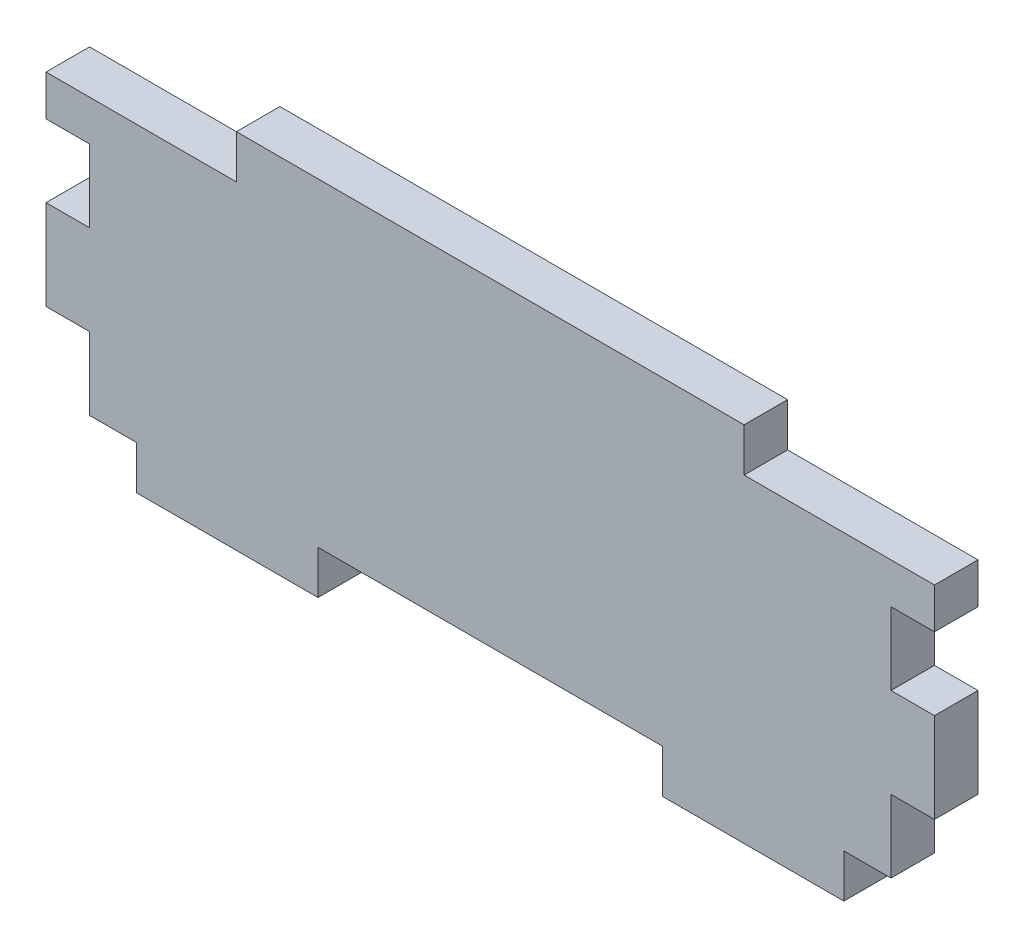
SolidWorks part; units mm, degrees
ref_plane "Front Plane" through (0, 0, 0) normal (0, 0, 1) x (1, 0, 0)
ref_plane "Top Plane" through (0, 0, 0) normal (0, 1, 0) x (1, 0, 0)
ref_plane "Right Plane" through (0, 0, 0) normal (1, 0, 0) x (0, 0, -1)
sketch "Sketch1" plane through (0, 0, 0) normal (0, 0, 1) x (1, 0, 0)
  line L0 (3.048, 9.8044) -> (0, 9.8044) construction
  line L1 (3.048, 16.1036) -> (3.048, 9.8044) construction
  line L2 (3.048, 16.1036) -> (0, 16.1036) construction
  line L3 (0, 21.1836) -> (0, 16.1036) construction
  line L4 (3.048, 21.1836) -> (0, 21.1836) construction
  line L5 (3.048, 24.0284) -> (3.048, 21.1836) construction
  line L7 (3.048, 9.8044) -> (0, 9.8044)
  line L8 (3.048, 16.1036) -> (3.048, 9.8044)
  line L9 (3.048, 16.1036) -> (0, 16.1036)
  line L10 (0, 21.1836) -> (0, 16.1036)
  line L11 (3.048, 21.1836) -> (0, 21.1836)
  line L12 (3.048, 24.0284) -> (3.048, 21.1836)
  line L13 (0, 9.8044) -> (0, 4.7244)
  line L14 (3.048, 24.0284) -> (-10.287, 24.0284)
  line L15 (-10.287, 24.0284) -> (-10.287, 27.0764)
  line L16 (-10.287, 27.0764) -> (-45.847, 27.0764)
  line L17 (-45.847, 27.0764) -> (-45.847, 24.0284)
  line L18 (-45.847, 24.0284) -> (-59.182, 24.0284)
  line L19 (-28.067, 27.0764) -> (-28.067, 4.7244) construction
  line L20 (-56.134, 9.8044) -> (-56.134, 4.7244)
  line L21 (-59.182, 24.0284) -> (-59.182, 21.1836)
  line L22 (-59.182, 21.1836) -> (-56.134, 21.1836)
  line L23 (-56.134, 21.1836) -> (-56.134, 16.1036)
  line L24 (-59.182, 16.1036) -> (-56.134, 16.1036)
  line L25 (-59.182, 16.1036) -> (-59.182, 9.8044)
  line L26 (-59.182, 9.8044) -> (-56.134, 9.8044)
  line L27 (0, 4.7244) -> (-3.302, 4.7244)
  line L28 (-3.302, 4.7244) -> (-3.302, 1.6764)
  line L29 (-3.302, 1.6764) -> (-16.002, 1.6764)
  line L30 (-16.002, 1.6764) -> (-16.002, 4.7244)
  line L31 (-16.002, 4.7244) -> (-40.132, 4.7244)
  line L32 (-40.132, 4.7244) -> (-40.132, 1.6764)
  line L33 (-40.132, 1.6764) -> (-52.832, 1.6764)
  line L34 (-52.832, 1.6764) -> (-52.832, 4.7244)
  line L35 (-52.832, 4.7244) -> (-56.134, 4.7244)
  dimension "D1" = 56.134
  dimension "D2" = 35.56
  dimension "D3" = 3.048
  dimension "D4" = 16.002
  dimension "D5" = 16.002
  dimension "D6" = 3.048
  dimension "D7" = 12.7
extrude "Boss-Extrude1" add sketch "Sketch1" along normal blind 3.048
